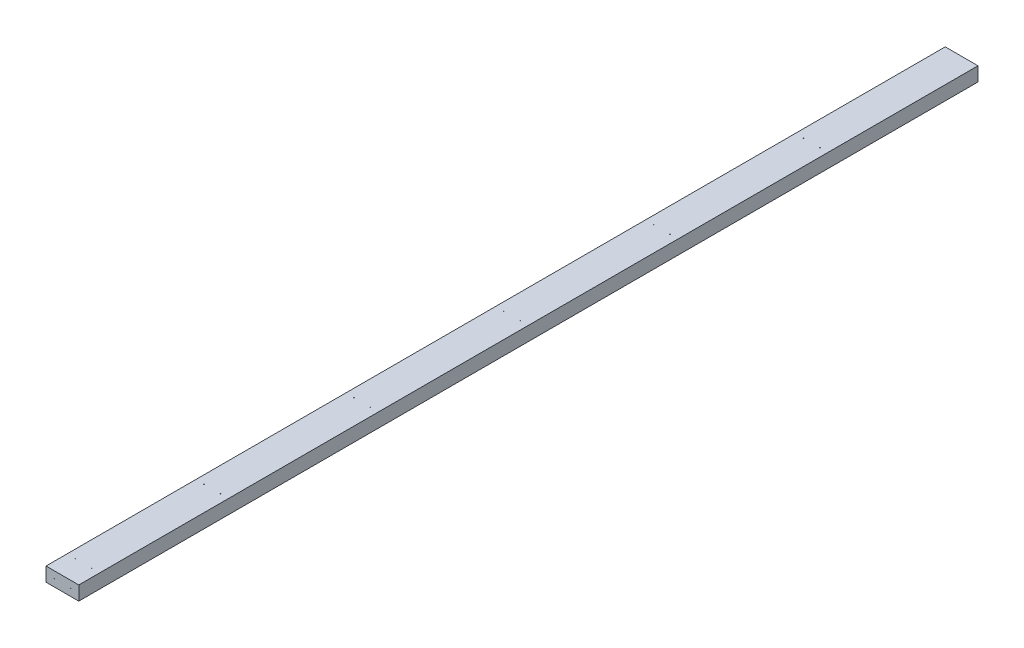
SolidWorks part; units mm, degrees
material "Pine"
ref_plane "Front Plane" through (0, 0, 0) normal (0, 0, 1) x (1, 0, 0)
ref_plane "Top Plane" through (0, 0, 0) normal (0, 1, 0) x (1, 0, 0)
ref_plane "Right Plane" through (0, 0, 0) normal (1, 0, 0) x (0, 0, -1)
sketch "Sketch1" plane through (0, 0, 0) normal (0, 0, 1) x (1, 0, 0)
  line L0 (0, 19.05) -> (44.45, 19.05) construction
  line L1 (0, 0) -> (88.9, 0)
  line L2 (0, 0) -> (0, 38.1)
  line L3 (0, 38.1) -> (88.9, 38.1)
  line L4 (88.9, 0) -> (88.9, 38.1)
  line L5 (44.45, 19.05) -> (88.9, 19.05) construction
  circle A0 centre (22.225, 19.05) radius 0.8763
  circle A1 centre (66.675, 19.05) radius 0.8763
  dimension "D3" = 1.7526
  dimension "D4" = 1.7526
  dimension "D1" = 88.9
  dimension "D2" = 38.1
extrude "Boss-Extrude1" add sketch "Sketch1" along normal blind 2438.4
sketch "Sketch3" plane through (0, 0, 0) normal (0, -1, 0) x (1, 0, 0)
  line L0 (0, 406.4) -> (44.45, 406.4) construction
  line L1 (0, 2438.4) -> (0, 0) construction
  line L2 (44.45, 406.4) -> (88.9, 406.4) construction
  line L3 (88.9, 2438.4) -> (88.9, 0) construction
  line L4 (0, 0) -> (88.9, 0) construction
  circle A0 centre (22.225, 406.4) radius 0.8763
  circle A1 centre (66.675, 406.4) radius 0.8763
  dimension "D2" = 1.7526
  dimension "D1" = 406.4
extrude "Cut-Extrude1" cut sketch "Sketch3" against normal up to surface (38.1 mm away) up to face at (44.45, 38.1, 1219.2)
pattern_linear "LPattern1" count 5 spacing 406.4 along (0, 0, 1) of "Cut-Extrude1"
sketch "Sketch4" plane through (0, 0, 0) normal (0, -1, 0) x (1, 0, 0)
  line L0 (44.45, 2381.25) -> (88.9, 2381.25) construction
  line L2 (88.9, 2438.4) -> (88.9, 0) construction
  line L3 (0, 2438.4) -> (88.9, 2438.4) construction
  line L4 (44.45, 2381.25) -> (0, 2381.25) construction
  line L5 (0, 2438.4) -> (0, 0) construction
  circle A0 centre (22.225, 2381.25) radius 0.8763
  circle A1 centre (66.675, 2381.25) radius 0.8763
  dimension "D2" = 1.7526
  dimension "D1" = 57.15
extrude "Cut-Extrude2" cut sketch "Sketch4" against normal up to surface (38.1 mm away) up to face at (66.675, 38.1, 2031.1237)
equation "\"length\"= 1219.2 * 2"
equation "\"D1@Boss-Extrude1\"=\"length\""
